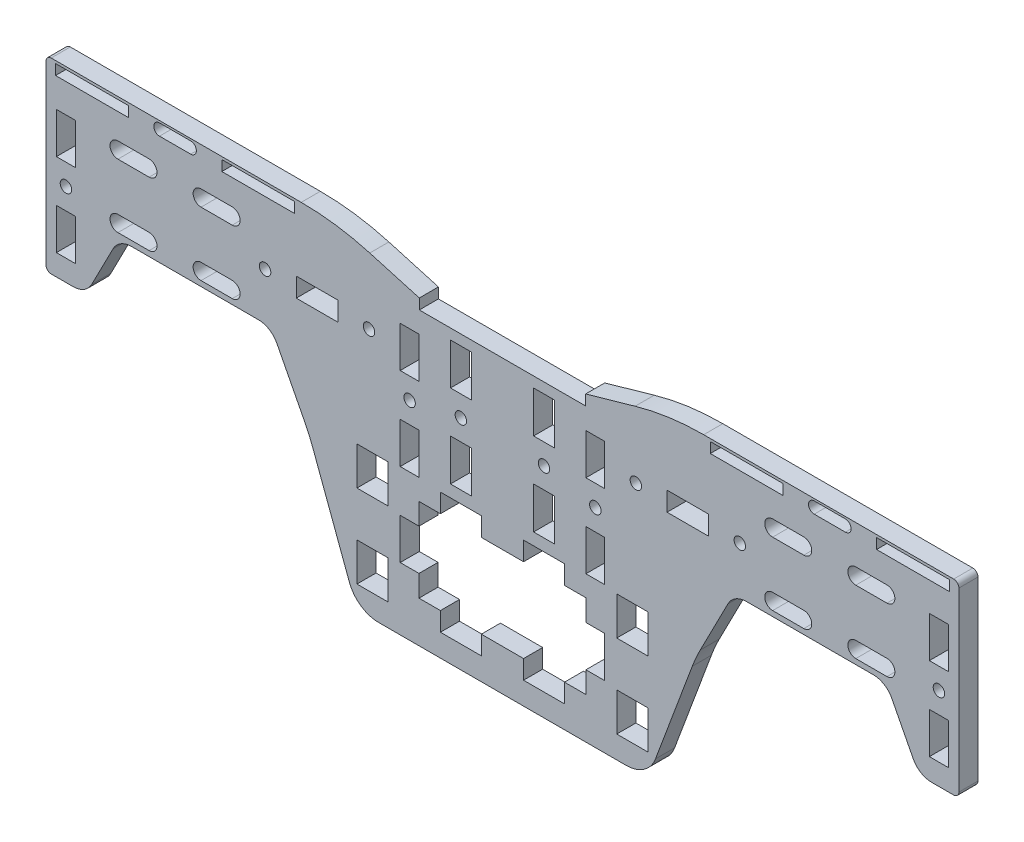
SolidWorks part; units mm, degrees
ref_plane "Front Plane" through (0, 0, 0) normal (0, 0, 1) x (1, 0, 0)
ref_plane "Top Plane" through (0, 0, 0) normal (0, 1, 0) x (1, 0, 0)
ref_plane "Right Plane" through (0, 0, 0) normal (1, 0, 0) x (0, 0, -1)
sketch "Sketch1" plane through (0, 0, 0) normal (0, 0, 1) x (1, 0, 0)
  line L0 (25.4, 66.675) -> (-25.4, 66.675) construction
  line L1 (25.5, -12.8) -> (18.95, -12.8)
  line L2 (25.5, -12.8) -> (25.5, -6.25)
  line L3 (-25.5, 12.8) -> (-18.95, 12.8)
  line L4 (-25.5, -12.8) -> (-25.5, -6.25)
  line L5 (25.5, -12.8) -> (-25.5, 12.8) construction
  line L6 (25.5, 12.8) -> (-25.5, -12.8) construction
  line L7 (0, 0) -> (0, 66.675) construction
  line L8 (25.4, 63.5) -> (-25.4, 63.5)
  line L9 (95.25, 101.6) -> (95.25, -30.1359) construction
  line L10 (19.05, 101.6) -> (171.45, 101.6) construction
  line L11 (171.45, 122.2375) -> (19.05, 122.2375) construction
  line L12 (171.45, 122.2375) -> (171.45, 80.9625) construction
  line L13 (171.45, 80.9625) -> (112.7125, 80.9625) construction
  line L14 (19.05, 122.2375) -> (19.05, 80.9625) construction
  line L15 (171.45, 122.2375) -> (19.05, 80.9625) construction
  line L16 (171.45, 80.9625) -> (19.05, 122.2375) construction
  line L17 (77.7875, 80.9625) -> (19.05, 80.9625) construction
  line L18 (77.7875, 69.9655) -> (74.2442, 69.9655) construction
  line L19 (112.7125, 69.9655) -> (112.7125, 80.9625) construction
  line L20 (63.246, 14.9745) -> (74.2442, 36.3359) construction
  line L21 (77.7875, 69.9655) -> (77.7875, 80.9625) construction
  line L22 (112.7125, 69.9655) -> (77.7875, 80.9625) construction
  line L23 (112.7125, 80.9625) -> (77.7875, 69.9655) construction
  line L24 (116.2558, 36.3359) -> (74.2442, 36.3359) construction
  line L25 (116.2558, 36.3359) -> (116.2558, 69.9655) construction
  line L26 (116.2558, 69.9655) -> (112.7125, 69.9655) construction
  line L27 (74.2442, 36.3359) -> (74.2442, 69.9655) construction
  line L28 (116.2558, 36.3359) -> (74.2442, 69.9655) construction
  line L29 (116.2558, 69.9655) -> (74.2442, 36.3359) construction
  line L30 (127.254, -75.2463) -> (63.246, -75.2463) construction
  line L31 (127.254, -75.2463) -> (127.254, 14.9745) construction
  line L32 (127.254, 14.9745) -> (63.246, 14.9745) construction
  line L33 (63.246, -75.2463) -> (63.246, 14.9745) construction
  line L34 (127.254, -75.2463) -> (63.246, 14.9745) construction
  line L35 (127.254, 14.9745) -> (63.246, -75.2463) construction
  line L36 (127.254, 14.9745) -> (116.2558, 36.3359) construction
  line L37 (74.2442, 59.7801) -> (116.2558, 59.7801) construction
  line L38 (74.2442, 40.3491) -> (116.2558, 40.3491) construction
  line L39 (-6.45, 12.8) -> (6.45, 12.8)
  line L40 (-6.45, 18.542) -> (-18.95, 18.542)
  line L41 (-6.45, 18.542) -> (-6.45, 12.8)
  line L42 (18.95, 18.542) -> (18.95, 12.8)
  line L43 (-18.95, 18.542) -> (-18.95, 12.8)
  line L44 (-6.45, 18.542) -> (-18.95, 12.8) construction
  line L45 (-6.45, 12.8) -> (-18.95, 18.542) construction
  line L46 (-25.5, 0) -> (25.5, 0) construction
  line L47 (6.45, 18.542) -> (6.45, 12.8)
  line L48 (6.45, 18.542) -> (18.95, 12.8) construction
  line L49 (6.45, 12.8) -> (18.95, 18.542) construction
  line L50 (6.45, 18.542) -> (18.95, 18.542)
  line L51 (18.95, 12.8) -> (25.5, 12.8)
  line L52 (44.45, -6.858) -> (34.925, -18.542) construction
  line L53 (44.45, 18.542) -> (34.925, 18.542)
  line L54 (44.45, 18.542) -> (44.45, 6.858)
  line L55 (44.45, 6.858) -> (34.925, 6.858)
  line L56 (34.925, 18.542) -> (34.925, 6.858)
  line L57 (44.45, 18.542) -> (34.925, 6.858) construction
  line L58 (44.45, 6.858) -> (34.925, 18.542) construction
  line L59 (44.45, -18.542) -> (34.925, -6.858) construction
  line L60 (34.925, -18.542) -> (34.925, -6.858)
  line L61 (44.45, -6.858) -> (34.925, -6.858)
  line L62 (44.45, -18.542) -> (44.45, -6.858)
  line L63 (44.45, -18.542) -> (34.925, -18.542)
  line L64 (-44.45, -18.542) -> (-34.925, -6.858) construction
  line L65 (-44.45, 6.858) -> (-34.925, 18.542) construction
  line L66 (-44.45, 18.542) -> (-34.925, 6.858) construction
  line L67 (0, 0) -> (0, -30.1681) construction
  line L68 (-44.45, -6.858) -> (-34.925, -18.542) construction
  line L69 (-44.45, -18.542) -> (-34.925, -18.542)
  line L70 (-44.45, -18.542) -> (-44.45, -6.858)
  line L71 (-44.45, -6.858) -> (-34.925, -6.858)
  line L72 (-34.925, -18.542) -> (-34.925, -6.858)
  line L73 (-34.925, 18.542) -> (-34.925, 6.858)
  line L74 (6.45, -12.8) -> (18.95, -18.542) construction
  line L75 (6.45, -18.542) -> (18.95, -12.8) construction
  line L76 (-6.45, -12.8) -> (-18.95, -18.542) construction
  line L77 (-6.45, -18.542) -> (-18.95, -12.8) construction
  line L78 (-44.45, 6.858) -> (-34.925, 6.858)
  line L79 (44.45, -25.4) -> (-44.45, -25.4)
  line L80 (-44.45, 18.542) -> (-44.45, 6.858)
  line L81 (-44.45, 18.542) -> (-34.925, 18.542)
  line L82 (-12.7, 63.5) -> (-12.7, 47.625) construction
  line L83 (-15.875, 22.225) -> (-9.525, 22.225)
  line L84 (-15.875, 47.625) -> (-9.525, 47.625)
  line L85 (-15.875, 47.625) -> (-15.875, 60.325)
  line L86 (-15.875, 60.325) -> (-9.525, 60.325)
  line L87 (-9.525, 47.625) -> (-9.525, 60.325)
  line L88 (-15.875, 47.625) -> (-9.525, 60.325) construction
  line L89 (-15.875, 60.325) -> (-9.525, 47.625) construction
  line L90 (6.45, -18.542) -> (18.95, -18.542)
  line L91 (6.45, -18.542) -> (6.45, -12.8)
  line L92 (-18.95, -18.542) -> (-18.95, -12.8)
  line L93 (18.95, -18.542) -> (18.95, -12.8)
  line L94 (-6.45, -18.542) -> (-6.45, -12.8)
  line L95 (-6.45, -18.542) -> (-18.95, -18.542)
  line L96 (-18.95, -12.8) -> (-25.5, -12.8)
  line L97 (6.45, -12.8) -> (-6.45, -12.8)
  line L98 (-25.5, 6.25) -> (-25.5, 12.8)
  line L99 (-31.242, -6.25) -> (-25.5, -6.25)
  line L100 (-31.242, -6.25) -> (-31.242, 6.25)
  line L101 (-31.242, 6.25) -> (-25.5, 6.25)
  line L102 (31.242, 6.25) -> (25.5, 6.25)
  line L103 (-31.242, -6.25) -> (-25.5, 6.25) construction
  line L104 (-31.242, 6.25) -> (-25.5, -6.25) construction
  line L105 (31.242, -6.25) -> (25.5, -6.25)
  line L106 (31.242, -6.25) -> (25.5, 6.25) construction
  line L107 (31.242, 6.25) -> (25.5, -6.25) construction
  line L108 (31.242, -6.25) -> (31.242, 6.25)
  line L109 (25.5, 6.25) -> (25.5, 12.8)
  line L110 (-15.875, 22.225) -> (-15.875, 34.925)
  line L111 (-15.875, 34.925) -> (-9.525, 34.925)
  line L112 (82.55, 59.7801) -> (92.075, 59.7801) construction
  line L113 (82.55, 62.1931) -> (92.075, 62.1931)
  line L114 (82.55, 57.3671) -> (92.075, 57.3671)
  line L115 (82.55, 40.3491) -> (92.075, 40.3491) construction
  line L116 (82.55, 42.7621) -> (92.075, 42.7621)
  line L117 (82.55, 37.9361) -> (92.075, 37.9361)
  line L118 (107.95, 59.7801) -> (117.475, 59.7801) construction
  line L119 (107.95, 62.1931) -> (117.475, 62.1931)
  line L120 (107.95, 57.3671) -> (117.475, 57.3671)
  line L121 (107.95, 40.3491) -> (117.475, 40.3491) construction
  line L122 (107.95, 42.7621) -> (117.475, 42.7621)
  line L123 (107.95, 37.9361) -> (117.475, 37.9361)
  line L124 (63.8955, 73.1405) -> (128.9432, 73.1405) construction
  line L125 (63.5, 73.1405) -> (76.2, 73.1405)
  line L126 (63.5, 73.1405) -> (63.5, 69.9655)
  line L127 (114.3, 73.1405) -> (127, 73.1405)
  line L128 (63.5, 69.9655) -> (76.2, 69.9655)
  line L129 (63.5, 69.9655) -> (76.2, 73.1405) construction
  line L130 (63.5, 73.1405) -> (76.2, 69.9655) construction
  line L131 (114.3, 69.9655) -> (127, 69.9655)
  line L132 (76.2, 73.1405) -> (85.725, 73.1405)
  line L133 (76.2, 69.9655) -> (85.725, 69.9655)
  line L134 (85.725, 73.1405) -> (85.725, 69.9655)
  line L135 (114.3, 73.1405) -> (114.3, 69.9655)
  line L136 (127, 73.1405) -> (136.525, 73.1405)
  line L137 (136.525, 73.1405) -> (136.525, 69.9655)
  line L138 (127, 69.9655) -> (136.525, 69.9655)
  line L139 (-28.371, 0) -> (-28.371, 63.5) construction
  line L140 (-31.242, 44.55) -> (-25.5, 44.55)
  line L141 (-31.242, 31.65) -> (-25.5, 31.65)
  line L142 (-31.242, 31.65) -> (-31.242, 19.15)
  line L143 (-31.242, 19.15) -> (-25.5, 19.15)
  line L144 (-25.5, 31.65) -> (-25.5, 19.15)
  line L145 (-31.242, 31.65) -> (-25.5, 19.15) construction
  line L146 (-31.242, 19.15) -> (-25.5, 31.65) construction
  line L147 (-31.242, 57.05) -> (-31.242, 44.55)
  line L148 (-31.242, 57.05) -> (-25.5, 57.05)
  line L149 (-25.5, 57.05) -> (-25.5, 44.55)
  line L150 (28.371, 0) -> (28.371, 63.5) construction
  line L151 (31.242, 19.15) -> (25.5, 31.65) construction
  line L152 (31.242, 31.65) -> (25.5, 19.15) construction
  line L153 (25.5, 57.05) -> (25.5, 44.55)
  line L154 (31.242, 57.05) -> (25.5, 57.05)
  line L155 (31.242, 57.05) -> (31.242, 44.55)
  line L156 (25.5, 31.65) -> (25.5, 19.15)
  line L157 (31.242, 19.15) -> (25.5, 19.15)
  line L158 (31.242, 31.65) -> (31.242, 19.15)
  line L159 (31.242, 31.65) -> (25.5, 31.65)
  line L160 (31.242, 44.55) -> (25.5, 44.55)
  line L161 (50.8, 73.9342) -> (139.446, 73.9342)
  line L162 (25.4, 63.5) -> (25.4, 66.675)
  line L163 (25.4, 66.675) -> (50.8, 73.9342)
  line L164 (44.45, -25.4) -> (59.0461, 13.7533)
  line L165 (70.6731, 36.3359) -> (117.1876, 36.3359)
  line L166 (59.0461, 13.7533) -> (70.6731, 36.3359)
  line L167 (133.35, 73.9342) -> (133.35, 48.6342) construction
  line L168 (60.4232, 16.4279) -> (71.4214, 37.7893) construction
  line L169 (130.429, 35.7342) -> (136.271, 35.7342)
  line L170 (-25.4, 63.5) -> (-25.4, 66.675)
  line L171 (-25.4, 66.675) -> (-50.8, 73.9342)
  line L172 (-63.5, 73.1405) -> (-76.2, 69.9655) construction
  line L173 (-63.5, 69.9655) -> (-76.2, 73.1405) construction
  line L174 (-63.8955, 73.1405) -> (-128.9432, 73.1405) construction
  line L175 (-74.2442, 40.3491) -> (-116.2558, 40.3491) construction
  line L176 (-74.2442, 59.7801) -> (-116.2558, 59.7801) construction
  line L177 (-127.254, 14.9745) -> (-116.2558, 36.3359) construction
  line L178 (-127.254, 14.9745) -> (-63.246, -75.2463) construction
  line L179 (-127.254, -75.2463) -> (-63.246, 14.9745) construction
  line L180 (-63.246, -75.2463) -> (-63.246, 14.9745) construction
  line L181 (-127.254, 14.9745) -> (-63.246, 14.9745) construction
  line L182 (-127.254, -75.2463) -> (-127.254, 14.9745) construction
  line L183 (-127.254, -75.2463) -> (-63.246, -75.2463) construction
  line L184 (-116.2558, 69.9655) -> (-74.2442, 36.3359) construction
  line L185 (-116.2558, 36.3359) -> (-74.2442, 69.9655) construction
  line L186 (-74.2442, 36.3359) -> (-74.2442, 69.9655) construction
  line L187 (-116.2558, 69.9655) -> (-112.7125, 69.9655) construction
  line L188 (-116.2558, 36.3359) -> (-116.2558, 69.9655) construction
  line L189 (-116.2558, 36.3359) -> (-74.2442, 36.3359) construction
  line L190 (-112.7125, 80.9625) -> (-77.7875, 69.9655) construction
  line L191 (-112.7125, 69.9655) -> (-77.7875, 80.9625) construction
  line L192 (-77.7875, 69.9655) -> (-77.7875, 80.9625) construction
  line L193 (-63.246, 14.9745) -> (-74.2442, 36.3359) construction
  line L194 (-112.7125, 69.9655) -> (-112.7125, 80.9625) construction
  line L195 (-77.7875, 69.9655) -> (-74.2442, 69.9655) construction
  line L196 (-77.7875, 80.9625) -> (-19.05, 80.9625) construction
  line L197 (-171.45, 80.9625) -> (-19.05, 122.2375) construction
  line L198 (-171.45, 122.2375) -> (-19.05, 80.9625) construction
  line L199 (-171.45, 80.9625) -> (-112.7125, 80.9625) construction
  line L200 (-171.45, 122.2375) -> (-171.45, 80.9625) construction
  line L201 (-171.45, 122.2375) -> (-19.05, 122.2375) construction
  line L202 (-19.05, 101.6) -> (-171.45, 101.6) construction
  line L203 (-95.25, 101.6) -> (-95.25, -30.1359) construction
  line L204 (130.429, 61.1342) -> (136.271, 61.1342)
  line L205 (130.429, 61.1342) -> (130.429, 48.6342)
  line L206 (-59.0461, 13.7533) -> (-70.6731, 36.3359)
  line L207 (-70.6731, 36.3359) -> (-117.1876, 36.3359)
  line L208 (-44.45, -25.4) -> (-59.0461, 13.7533)
  line L209 (-50.8, 73.9342) -> (-139.446, 73.9342)
  line L210 (-127, 69.9655) -> (-136.525, 69.9655)
  line L211 (-136.525, 73.1405) -> (-136.525, 69.9655)
  line L212 (-127, 73.1405) -> (-136.525, 73.1405)
  line L213 (-114.3, 73.1405) -> (-114.3, 69.9655)
  line L214 (-85.725, 73.1405) -> (-85.725, 69.9655)
  line L215 (-76.2, 69.9655) -> (-85.725, 69.9655)
  line L216 (-76.2, 73.1405) -> (-85.725, 73.1405)
  line L217 (-114.3, 69.9655) -> (-127, 69.9655)
  line L218 (-63.5, 69.9655) -> (-76.2, 69.9655)
  line L219 (-114.3, 73.1405) -> (-127, 73.1405)
  line L220 (-63.5, 73.1405) -> (-63.5, 69.9655)
  line L221 (-63.5, 73.1405) -> (-76.2, 73.1405)
  line L222 (-107.95, 40.3491) -> (-117.475, 40.3491) construction
  line L223 (-107.95, 42.7621) -> (-117.475, 42.7621)
  line L224 (-107.95, 37.9361) -> (-117.475, 37.9361)
  line L225 (-107.95, 59.7801) -> (-117.475, 59.7801) construction
  line L226 (-107.95, 62.1931) -> (-117.475, 62.1931)
  line L227 (-107.95, 57.3671) -> (-117.475, 57.3671)
  line L228 (-82.55, 40.3491) -> (-92.075, 40.3491) construction
  line L229 (-82.55, 42.7621) -> (-92.075, 42.7621)
  line L230 (-82.55, 37.9361) -> (-92.075, 37.9361)
  line L231 (-82.55, 59.7801) -> (-92.075, 59.7801) construction
  line L232 (-82.55, 62.1931) -> (-92.075, 62.1931)
  line L233 (-82.55, 57.3671) -> (-92.075, 57.3671)
  line L234 (-19.05, 122.2375) -> (-19.05, 80.9625) construction
  line L235 (-25.5, 44.55) -> (-25.5, 31.65) construction
  line L236 (25.5, 31.65) -> (25.5, 44.55) construction
  line L237 (-25.5, 38.1) -> (25.5, 38.1) construction
  line L238 (-9.525, 22.225) -> (-9.525, 34.925)
  line L239 (-15.875, 22.225) -> (-9.525, 34.925) construction
  line L240 (-15.875, 34.925) -> (-9.525, 22.225) construction
  line L241 (-12.7, 34.925) -> (-12.7, 18.542) construction
  line L242 (-12.7, 47.625) -> (-12.7, 34.925) construction
  line L243 (12.7, 47.625) -> (12.7, 34.925) construction
  line L244 (15.875, 34.925) -> (9.525, 22.225) construction
  line L245 (15.875, 22.225) -> (9.525, 34.925) construction
  line L246 (15.875, 60.325) -> (9.525, 47.625) construction
  line L247 (15.875, 47.625) -> (9.525, 60.325) construction
  line L248 (9.525, 22.225) -> (9.525, 34.925)
  line L249 (15.875, 34.925) -> (9.525, 34.925)
  line L250 (15.875, 22.225) -> (15.875, 34.925)
  line L251 (9.525, 47.625) -> (9.525, 60.325)
  line L252 (15.875, 60.325) -> (9.525, 60.325)
  line L253 (15.875, 47.625) -> (15.875, 60.325)
  line L254 (15.875, 47.625) -> (9.525, 47.625)
  line L255 (15.875, 22.225) -> (9.525, 22.225)
  line L256 (-116.2558, 50.75) -> (-74.2442, 50.75) construction
  line L257 (-85.725, 71.553) -> (-114.3, 71.553) construction
  line L258 (-95.25, 71.553) -> (-104.775, 71.553) construction
  line L259 (-95.25, 69.8004) -> (-104.775, 69.8004)
  line L260 (-95.25, 73.3056) -> (-104.775, 73.3056)
  line L261 (50.292, 53.671) -> (50.292, 47.829)
  line L262 (-62.992, 53.671) -> (-50.292, 53.671)
  line L263 (-62.992, 53.671) -> (-62.992, 47.829)
  line L264 (-62.992, 47.829) -> (-50.292, 47.829)
  line L265 (-50.292, 53.671) -> (-50.292, 47.829)
  line L266 (-62.992, 53.671) -> (-50.292, 47.829) construction
  line L267 (-62.992, 47.829) -> (-50.292, 53.671) construction
  line L268 (62.992, 53.671) -> (50.292, 47.829) construction
  line L269 (62.992, 47.829) -> (50.292, 53.671) construction
  line L270 (62.992, 47.829) -> (50.292, 47.829)
  line L271 (62.992, 53.671) -> (62.992, 47.829)
  line L272 (62.992, 53.671) -> (50.292, 53.671)
  line L273 (95.25, 71.553) -> (104.775, 71.553) construction
  line L274 (95.25, 69.8004) -> (104.775, 69.8004)
  line L275 (95.25, 73.3056) -> (104.775, 73.3056)
  line L276 (-56.642, 47.829) -> (-56.642, 53.671) construction
  line L277 (130.429, 48.6342) -> (136.271, 48.6342)
  line L278 (136.271, 61.1342) -> (136.271, 48.6342)
  line L279 (130.429, 61.1342) -> (136.271, 48.6342) construction
  line L280 (130.429, 48.6342) -> (136.271, 61.1342) construction
  line L281 (130.429, 35.7342) -> (130.429, 23.2342)
  line L282 (130.429, 23.2342) -> (136.271, 23.2342)
  line L283 (136.271, 35.7342) -> (136.271, 23.2342)
  line L284 (133.35, 35.7342) -> (133.35, 23.2342) construction
  line L285 (130.429, 35.7342) -> (136.271, 23.2342) construction
  line L286 (130.429, 23.2342) -> (136.271, 35.7342) construction
  line L287 (133.35, 35.7342) -> (133.35, 27.5161) construction
  line L288 (133.35, 35.7342) -> (133.35, 48.6342) construction
  line L289 (139.446, 73.9342) -> (139.446, 16.7842)
  line L290 (139.446, 16.7842) -> (127.254, 16.7842)
  line L291 (127.254, 16.7842) -> (117.1876, 36.3359)
  line L292 (-127.254, 16.7842) -> (-117.1876, 36.3359)
  line L293 (-139.446, 16.7842) -> (-127.254, 16.7842)
  line L294 (-139.446, 73.9342) -> (-139.446, 16.7842)
  line L295 (-133.35, 35.7342) -> (-133.35, 48.6342) construction
  line L296 (-133.35, 35.7342) -> (-133.35, 27.5161) construction
  line L297 (-130.429, 23.2342) -> (-136.271, 35.7342) construction
  line L298 (-130.429, 35.7342) -> (-136.271, 23.2342) construction
  line L299 (-133.35, 35.7342) -> (-133.35, 23.2342) construction
  line L300 (-130.429, 48.6342) -> (-136.271, 61.1342) construction
  line L301 (-130.429, 61.1342) -> (-136.271, 48.6342) construction
  line L302 (-136.271, 35.7342) -> (-136.271, 23.2342)
  line L303 (-130.429, 23.2342) -> (-136.271, 23.2342)
  line L304 (-130.429, 35.7342) -> (-130.429, 23.2342)
  line L305 (-136.271, 61.1342) -> (-136.271, 48.6342)
  line L306 (-130.429, 48.6342) -> (-136.271, 48.6342)
  line L307 (-130.429, 61.1342) -> (-130.429, 48.6342)
  line L308 (-130.429, 61.1342) -> (-136.271, 61.1342)
  line L309 (-130.429, 35.7342) -> (-136.271, 35.7342)
  circle A0 centre (82.55, 59.7801) radius 2.413 construction
  circle A1 centre (107.95, 59.7801) radius 2.413 construction
  circle A2 centre (82.55, 40.3491) radius 2.413 construction
  circle A3 centre (107.95, 40.3491) radius 2.413 construction
  arc A4 (82.55, 62.1931) -> (82.55, 57.3671) centre (82.55, 59.7801) ccw
  arc A5 (92.075, 57.3671) -> (92.075, 62.1931) centre (92.075, 59.7801) ccw
  arc A6 (82.55, 42.7621) -> (82.55, 37.9361) centre (82.55, 40.3491) ccw
  arc A7 (92.075, 37.9361) -> (92.075, 42.7621) centre (92.075, 40.3491) ccw
  arc A8 (107.95, 62.1931) -> (107.95, 57.3671) centre (107.95, 59.7801) ccw
  arc A9 (117.475, 57.3671) -> (117.475, 62.1931) centre (117.475, 59.7801) ccw
  arc A10 (107.95, 42.7621) -> (107.95, 37.9361) centre (107.95, 40.3491) ccw
  arc A11 (117.475, 37.9361) -> (117.475, 42.7621) centre (117.475, 40.3491) ccw
  circle A12 centre (-107.95, 40.3491) radius 2.413 construction
  circle A13 centre (-82.55, 40.3491) radius 2.413 construction
  circle A14 centre (-107.95, 59.7801) radius 2.413 construction
  circle A15 centre (-82.55, 59.7801) radius 2.413 construction
  arc A16 (-107.95, 42.7621) -> (-107.95, 37.9361) centre (-107.95, 40.3491) cw
  arc A17 (-117.475, 37.9361) -> (-117.475, 42.7621) centre (-117.475, 40.3491) cw
  arc A18 (-107.95, 62.1931) -> (-107.95, 57.3671) centre (-107.95, 59.7801) cw
  arc A19 (-117.475, 57.3671) -> (-117.475, 62.1931) centre (-117.475, 59.7801) cw
  arc A20 (-82.55, 42.7621) -> (-82.55, 37.9361) centre (-82.55, 40.3491) cw
  arc A21 (-92.075, 37.9361) -> (-92.075, 42.7621) centre (-92.075, 40.3491) cw
  arc A22 (-82.55, 62.1931) -> (-82.55, 57.3671) centre (-82.55, 59.7801) cw
  arc A23 (-92.075, 57.3671) -> (-92.075, 62.1931) centre (-92.075, 59.7801) cw
  circle A24 centre (0, 101.6) radius 34.925 construction
  circle A25 centre (28.371, 38.1) radius 1.7526
  circle A26 centre (-28.371, 38.1) radius 1.7526
  circle A27 centre (-12.7, 41.275) radius 1.7526
  circle A28 centre (12.7, 41.275) radius 1.7526
  arc A29 (-95.25, 69.8004) -> (-95.25, 73.3056) centre (-95.25, 71.553) ccw
  arc A30 (-104.775, 73.3056) -> (-104.775, 69.8004) centre (-104.775, 71.553) ccw
  arc A31 (95.25, 69.8004) -> (95.25, 73.3056) centre (95.25, 71.553) cw
  arc A32 (104.775, 73.3056) -> (104.775, 69.8004) centre (104.775, 71.553) cw
  circle A33 centre (-72.517, 50.75) radius 1.7526
  circle A34 centre (-40.767, 50.75) radius 1.7526
  circle A35 centre (40.767, 50.75) radius 1.7526
  circle A36 centre (72.517, 50.75) radius 1.7526
  circle A37 centre (133.35, 42.1842) radius 1.7526
  circle A38 centre (-133.35, 42.1842) radius 1.7526
  point P0 (0, 0)
  point P9 (0, 66.675)
  point P14 (0, 63.5)
  point P22 (95.25, 75.464)
  point P27 (95.25, 53.1507)
  point P45 (39.6875, 12.7)
  point P49 (-12.7, 15.671)
  point P60 (12.7, 15.671)
  point P63 (0, 15.671)
  point P70 (39.6875, -12.7)
  point P79 (-39.6875, -12.7)
  point P80 (-39.6875, 12.7)
  point P83 (-12.7, 53.975)
  point P97 (-12.7, 28.575)
  point P100 (0, -15.671)
  point P101 (12.7, -15.671)
  point P102 (-12.7, -15.671)
  point P104 (-28.371, 0)
  point P113 (28.371, 0)
  point P118 (0, -25.4)
  point P119 (87.3125, 59.7801)
  point P124 (87.3125, 40.3491)
  point P135 (112.7125, 59.7801)
  point P140 (112.7125, 40.3491)
  point P146 (69.85, 71.553)
  point P161 (-28.371, 25.4)
  point P180 (28.371, 25.4)
  point P241 (-69.85, 71.553)
  point P243 (-112.7125, 40.3491)
  point P249 (-112.7125, 59.7801)
  point P255 (-87.3125, 40.3491)
  point P261 (-87.3125, 59.7801)
  point P266 (-95.25, 53.1507)
  point P267 (-95.25, 75.464)
  point P292 (12.7, 28.575)
  point P293 (12.7, 53.975)
  point P300 (-100.0125, 71.553)
  point P305 (-56.642, 50.75)
  point P316 (100.0125, 71.553)
  point P331 (133.35, 54.8842)
  point P340 (133.35, 29.4842)
  point P364 (-133.35, 29.4842)
  point P365 (-133.35, 54.8842)
  dimension "D17" = 4.826
  dimension "D33" = 2.413
  dimension "D34" = 2.413
  dimension "D53" = 69.85
  dimension "D56" = 3.5052
  dimension "D61" = 3.5052
  dimension "D64" = 1.7526
  dimension "D69" = 3.5052
  dimension "D74" = 3.5052
  dimension "D1" = 25.6
  dimension "D2" = 51
  dimension "D3" = 50.8
  dimension "D4" = 66.675
  dimension "D5" = 3.175
  dimension "D6" = 152.4
  dimension "D7" = 41.275
  dimension "D8" = 38.1
  dimension "D9" = 19.05
  dimension "D10" = 10.997
  dimension "D11" = 42.0116
  dimension "D12" = 33.6296
  dimension "D13" = 64.008
  dimension "D14" = 90.2208
  dimension "D15" = 21.3614
  dimension "D16" = 10.1854
  dimension "D18" = 12.7
  dimension "D19" = 19.431
  dimension "D21" = 12.7
  dimension "D22" = 5.742
  dimension "D23" = 12.5
  dimension "D24" = 9.525
  dimension "D25" = 11.684
  dimension "D26" = 39.6875
  dimension "D27" = 6.35
  dimension "D28" = 5.742
  dimension "D29" = 12.5
  dimension "D30" = 25.4
  dimension "D31" = 88.9
  dimension "D32" = 9.525
  dimension "D35" = 9.525
  dimension "D37" = 34.925
  dimension "D38" = 3.175
  dimension "D39" = 3.175
  dimension "D40" = 12.7
  dimension "D41" = 25.4
  dimension "D42" = 9.525
  dimension "D44" = 5.742
  dimension "D45" = 12.5
  dimension "D46" = 25.4
  dimension "D48" = 1.5875
  dimension "D49" = 25.4
  dimension "D51" = 12.192
  dimension "D52" = 3.175
  dimension "D54" = 101.6
  dimension "D55" = 25.4
  dimension "D57" = 9.525
  dimension "D58" = 12.7
  dimension "D59" = 12.7
  dimension "D62" = 23.1843
  dimension "D63" = 9.525
  dimension "D65" = 19.05
  dimension "D66" = 12.7
  dimension "D67" = 5.842
  dimension "D68" = 15.875
  dimension "D70" = 5.842
  dimension "D71" = 12.5
  dimension "D73" = 19.05
  dimension "D75" = 38.1
  dimension "D76" = 12.7
  dimension "D50" = 3.175
  dimension "D20" = 2
  dimension "D36" = 2
  dimension "D43" = 2
  dimension "D47" = 2
  dimension "D60" = 2
  dimension "D72" = 2
extrude "Boss-Extrude1" add sketch "Sketch1" along normal blind 5.842
fillet "Fillet1" radius 6.35 2 edges at (70.6731, 36.3359, 2.921) (-70.6731, 36.3359, 2.921)
fillet "Fillet2" radius 9.525 2 edges at (-44.45, -25.4, 2.921) (44.45, -25.4, 2.921)
fillet "Fillet4" radius 76.2 2 edges at (50.8, 73.9342, 2.921) (-50.8, 73.9342, 2.921)
fillet "Fillet5" radius 50.8 2 edges at (59.0461, 13.7533, 2.921) (-59.0461, 13.7533, 2.921)
sketch "Sketch2" [suppressed] plane through (0, 0, 5.842) normal (0, 0, 1) x (1, 0, 0)
  line L0 (44.45, 6.858) -> (44.45, 18.542) construction
  line L1 (-44.45, 18.542) -> (-34.925, 18.542)
  line L2 (-44.45, 18.542) -> (-44.45, -18.542)
  line L3 (-44.45, -18.542) -> (-34.925, -18.542)
  line L4 (-34.925, 18.542) -> (-34.925, -18.542)
  line L5 (34.925, -18.542) -> (44.45, -18.542)
  line L6 (34.925, -18.542) -> (34.925, 18.542)
  line L7 (34.925, 18.542) -> (44.45, 18.542)
  line L8 (44.45, -18.542) -> (44.45, 18.542)
extrude "Boss-Extrude2" [suppressed] add sketch "Sketch2" against normal up to surface (5.842 mm away) up to face at (-133.35, 54.8842, 0)
sketch "Sketch3" [suppressed] plane through (0, 0, 5.842) normal (0, 0, 1) x (1, 0, 0)
  line L0 (0, 63.5) -> (0, -25.4) construction
  line L1 (-77.0183, 57.907) -> (-37.2922, 57.907)
  line L2 (-77.0183, 57.907) -> (-77.0183, 44.7899)
  line L3 (-77.0183, 44.7899) -> (-37.2922, 44.7899)
  line L4 (-37.2922, 57.907) -> (-37.2922, 44.7899)
  line L5 (-31.242, 57.05) -> (-25.5, 57.05)
  line L6 (-31.242, 57.05) -> (-31.242, 19.15)
  line L8 (-25.5, 57.05) -> (-25.5, 19.15)
  line L9 (25.4, 63.5) -> (-25.4, 63.5) construction
  line L10 (-37.8355, -25.4) -> (37.8355, -25.4) construction
  line L11 (25.5, 57.05) -> (25.5, 19.15)
  line L13 (31.242, 57.05) -> (31.242, 19.15)
  line L14 (31.242, 57.05) -> (25.5, 57.05)
  line L15 (37.2922, 57.907) -> (37.2922, 44.7899)
  line L16 (77.0183, 44.7899) -> (37.2922, 44.7899)
  line L17 (77.0183, 57.907) -> (77.0183, 44.7899)
  line L18 (77.0183, 57.907) -> (37.2922, 57.907)
  line L21 (-31.242, 19.15) -> (-31.242, -6.25)
  line L22 (-31.242, -6.25) -> (-25.5, -6.25)
  line L23 (-25.5, 19.15) -> (-25.5, -6.25)
  line L24 (25.5, -6.25) -> (31.242, -6.25)
  line L25 (25.5, -6.25) -> (25.5, 19.15)
  line L27 (31.242, -6.25) -> (31.242, 19.15)
extrude "Boss-Extrude3" [suppressed] add sketch "Sketch3" against normal up to surface (5.842 mm away) up to face at (-133.35, 54.8842, 0)
fillet "Fillet6" radius 6.35 4 edges at (-127.254, 16.7842, 2.921) (127.254, 16.7842, 2.921) (117.1876, 36.3359, 2.921) (-117.1876, 36.3359, 2.921)
fillet "Fillet7" radius 1.5875 4 edges at (139.446, 16.7842, 2.921) (139.446, 73.9342, 2.921) (-139.446, 73.9342, 2.921) (-139.446, 16.7842, 2.921)
